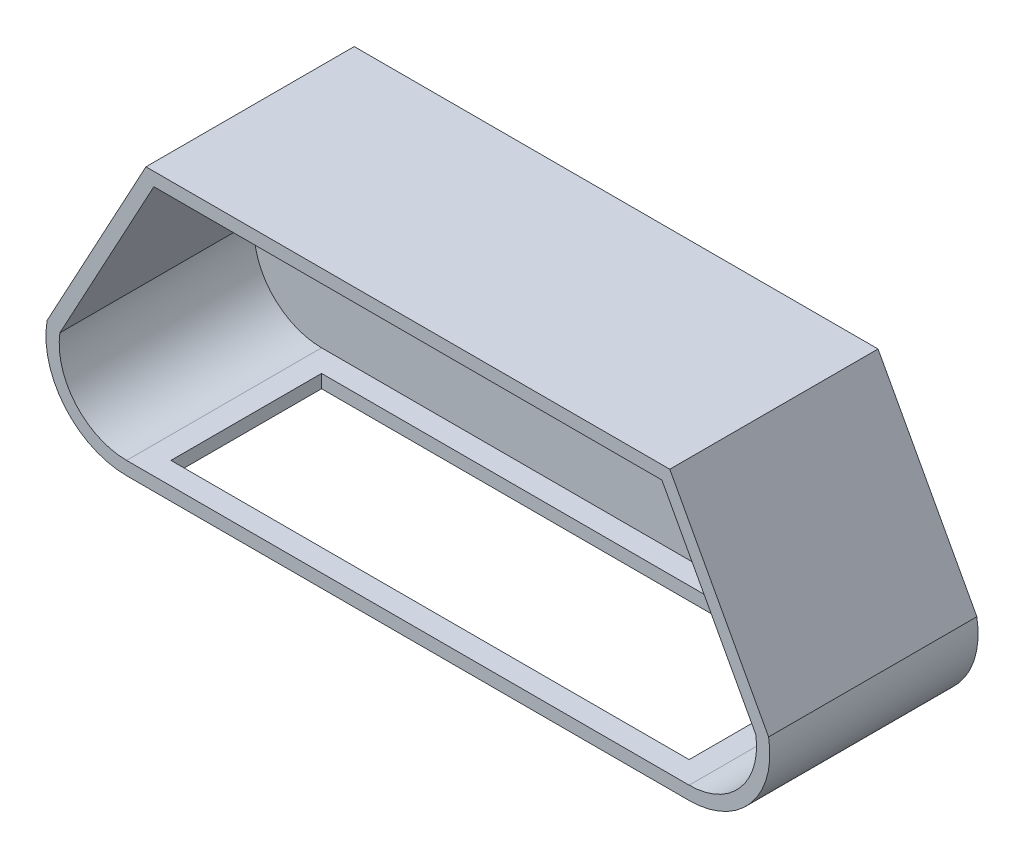
SolidWorks part; units mm, degrees
material "ABS"
ref_plane "Front Plane" through (0, 0, 0) normal (0, 0, 1) x (1, 0, 0)
ref_plane "Top Plane" through (0, 0, 0) normal (0, 1, 0) x (1, 0, 0)
ref_plane "Right Plane" through (0, 0, 0) normal (1, 0, 0) x (0, 0, -1)
sketch "Sketch1" plane through (0, 0, 0) normal (0, 0, 1) x (1, 0, 0)
  line L0 (101.3496, 25.9543) -> (-100.0805, 25.9543) construction
  line L1 (-100.0805, 25.9543) -> (-119.9586, -10.7438) construction
  line L2 (-119.9586, -10.7438) -> (121.2277, -10.7438) construction
  line L3 (121.2277, -10.7438) -> (101.3496, 25.9543) construction
  line L4 (98.8617, 30.5473) -> (-98.0902, 30.5473) construction
  line L5 (-98.0902, 30.5473) -> (-100.0805, 25.9543) construction
  line L6 (-100.0805, 25.9543) -> (101.3496, 25.9543) construction
  line L7 (101.3496, 25.9543) -> (98.8617, 30.5473) construction
  line L8 (121.2774, -10.8357) -> (-120.0083, -10.8357) construction
  line L9 (-120.0083, -10.8357) -> (-124.9592, -19.9757) construction
  line L10 (-124.9592, -19.9757) -> (126.2283, -19.9757) construction
  line L11 (126.2283, -19.9757) -> (121.2774, -10.8357) construction
  line L12 (126.2283, -19.9757) -> (-124.9592, -19.9757) construction
  line L13 (-124.9592, -19.9757) -> (-126.9495, -24.5687) construction
  line L14 (-126.9495, -24.5687) -> (128.7162, -24.5687) construction
  line L15 (128.7162, -24.5687) -> (126.2283, -19.9757) construction
  line L16 (-0.0149, 8.8786) -> (-0.0149, 16.2511) construction
  line L17 (-0.0149, 16.2511) -> (-21.6189, 32.8696) construction
  line L18 (-39.0554, 18.8331) -> (-15.5065, 0.7186) construction
  line L19 (-15.5065, 0.7186) -> (-8.5158, 0.7186) construction
  line L20 (-21.6189, 32.8696) -> (-0.0149, 16.2511) construction
  line L21 (-0.0149, 16.2511) -> (21.5891, 32.8696) construction
  line L22 (21.5891, 32.8696) -> (-21.6189, 32.8696) construction
  line L23 (-0.0149, 16.2511) -> (-0.0149, 8.8786) construction
  line L24 (8.4859, 0.7186) -> (15.4767, 0.7186) construction
  line L25 (15.4767, 0.7186) -> (39.0256, 18.8331) construction
  line L26 (21.5891, 32.8696) -> (-0.0149, 16.2511) construction
  line L27 (-0.0149, -7.4414) -> (-0.0149, -14.814) construction
  line L28 (-0.0149, -14.814) -> (21.5891, -31.4324) construction
  line L29 (39.0256, -17.396) -> (15.4767, 0.7186) construction
  line L30 (15.4767, 0.7186) -> (8.4859, 0.7186) construction
  line L31 (-0.0149, -14.814) -> (-0.0149, -7.4414) construction
  line L32 (-8.5158, 0.7186) -> (-15.5065, 0.7186) construction
  line L33 (-15.5065, 0.7186) -> (-39.0554, -17.396) construction
  line L34 (-21.6189, -31.4324) -> (-0.0149, -14.814) construction
  line L35 (21.5891, -31.4324) -> (-0.0149, -14.814) construction
  line L36 (-0.0149, -14.814) -> (-21.6189, -31.4324) construction
  line L37 (-21.6189, -31.4324) -> (21.5891, -31.4324) construction
  line L38 (0, 0) -> (0, -40) construction
  line L55 (118.2148, 64.1367) -> (-118.2148, 64.1367)
  line L56 (-162.8226, -18.2161) -> (-118.2148, 64.1367)
  line L57 (126.9495, -61) -> (-126.9495, -61)
  line L58 (162.8226, -18.2161) -> (118.2148, 64.1367)
  line L59 (114.6411, 58.1367) -> (-114.6411, 58.1367)
  line L60 (-157.0626, -20.1798) -> (-114.6411, 58.1367)
  line L61 (126.9495, -55) -> (-126.9495, -55)
  line L62 (157.0626, -20.1798) -> (114.6411, 58.1367)
  arc A7 (-126.9495, -61) -> (-162.8226, -18.2161) centre (-126.9495, -24.5687) cw
  arc A8 (126.9495, -61) -> (162.8226, -18.2161) centre (126.9495, -24.5687) ccw
  arc A9 (-126.9495, -55) -> (-157.0626, -20.1798) centre (-126.9495, -24.5687) cw
  arc A10 (126.9495, -55) -> (157.0626, -20.1798) centre (126.9495, -24.5687) ccw
  ellipse E0 centre (89.7353, -69.7395) end of major axis (186.1017, -143.8674) minor radius 36.744 (-8.4299, 0.9831) -> (-8.5158, 0.7186) ccw construction
  ellipse E1 centre (-34.244, 25.6292) end of major axis (23.2497, 27.2434) minor radius 7.0609 (-21.6189, 32.8696) -> (-29.9018, 32.7928) ccw construction
  ellipse E2 centre (-29.4366, 21.9312) end of major axis (-30.126, -23.328) minor radius 9.5952 (-38.9944, 23.9309) -> (-39.0554, 18.8331) ccw construction
  ellipse E3 centre (-89.7652, -69.7395) end of major axis (-186.1315, -143.8674) minor radius 36.744 (8.4859, 0.7186) -> (8.4, 0.9831) ccw construction
  ellipse E4 centre (29.4068, 21.9312) end of major axis (28.7173, 67.1904) minor radius 9.5952 (39.0256, 18.8331) -> (38.9645, 23.9309) ccw construction
  ellipse E5 centre (34.2141, 25.6292) end of major axis (91.7078, 24.015) minor radius 7.0609 (29.872, 32.7928) -> (21.5891, 32.8696) ccw construction
  ellipse E6 centre (-89.7652, 71.1766) end of major axis (-186.1315, 145.3046) minor radius 36.744 (8.4, 0.4541) -> (8.4859, 0.7186) ccw construction
  ellipse E7 centre (34.2141, -24.1921) end of major axis (91.7078, -22.5778) minor radius 7.0609 (21.5891, -31.4324) -> (29.872, -31.3556) ccw construction
  ellipse E8 centre (29.4068, -20.4941) end of major axis (28.7173, -65.7533) minor radius 9.5952 (38.9645, -22.4938) -> (39.0256, -17.396) ccw construction
  ellipse E9 centre (89.7353, 71.1766) end of major axis (186.1017, 145.3046) minor radius 36.744 (-8.5158, 0.7186) -> (-8.4299, 0.4541) ccw construction
  ellipse E10 centre (-29.4366, -20.4941) end of major axis (-30.126, 24.7651) minor radius 9.5952 (-39.0554, -17.396) -> (-38.9944, -22.4938) ccw construction
  ellipse E11 centre (-34.244, -24.1921) end of major axis (-91.7377, -22.5778) minor radius 7.0609 (-29.9018, -31.3556) -> (-21.6189, -31.4324) ccw construction
  spline S0 degree 3 poles (-8.4299, 0.9831) (-8.3473, 1.2284) (-8.2786, 1.4779) (-8.1305, 1.9735) (-8.0532, 2.2202) (-7.7992, 2.9534) (-7.601, 3.4303) (-7.1352, 4.3396) (-6.8677, 4.7742) (-6.2562, 5.5989) (-5.9092, 5.991) (-5.1648, 6.6958) (-4.7647, 7.013) (-3.91, 7.5786) (-3.451, 7.8283) (-2.509, 8.2452) (-2.0243, 8.4142) (-1.0325, 8.6872) (-0.5243, 8.7893) (-0.0149, 8.8786) knots 0 0 0 0 0.0625 0.0625 0.125 0.125 0.25 0.25 0.375 0.375 0.5 0.5 0.625 0.625 0.75 0.75 0.875 0.875 1 1 1 1 construction
  spline S1 degree 3 poles (-29.9018, 32.7928) (-30.49, 32.782) (-31.0692, 32.7181) (-31.9248, 32.5449) (-32.2077, 32.4742) (-32.769, 32.3061) (-33.0487, 32.208) (-33.8657, 31.8778) (-34.3832, 31.6099) (-35.1186, 31.1362) (-35.3569, 30.9662) (-35.8192, 30.6011) (-36.042, 30.4067) (-36.6741, 29.7983) (-37.0523, 29.3558) (-37.554, 28.6361) (-37.7109, 28.3855) (-37.998, 27.8717) (-38.1278, 27.6096) (-38.4772, 26.8083) (-38.6573, 26.2539) (-38.8469, 25.3922) (-38.8962, 25.1012) (-38.9663, 24.5182) (-38.9874, 24.2252) (-38.9944, 23.9309) knots 0 0 0 0 0.125 0.125 0.1875 0.1875 0.25 0.25 0.375 0.375 0.4375 0.4375 0.5 0.5 0.625 0.625 0.6875 0.6875 0.75 0.75 0.875 0.875 0.9375 0.9375 1 1 1 1 construction
  spline S2 degree 3 poles (-0.0149, 8.8786) (0.4936, 8.7894) (0.9992, 8.688) (1.9949, 8.4141) (2.4823, 8.2438) (3.416, 7.8307) (3.8648, 7.5877) (4.5082, 7.1636) (4.7189, 7.0113) (5.1236, 6.6907) (5.3175, 6.5226) (5.8747, 5.9957) (6.2134, 5.6143) (6.8262, 4.7918) (7.1004, 4.3485) (7.571, 3.4312) (7.7697, 2.9525) (8.0235, 2.2198) (8.1007, 1.9731) (8.2488, 1.4777) (8.3175, 1.2283) (8.4, 0.9831) knots 0 0 0 0 0.125 0.125 0.25 0.25 0.375 0.375 0.4375 0.4375 0.5 0.5 0.625 0.625 0.75 0.75 0.875 0.875 0.9375 0.9375 1 1 1 1 construction
  spline S3 degree 3 poles (38.9645, 23.9309) (38.9505, 24.5193) (38.8809, 25.0976) (38.6947, 25.9499) (38.619, 26.2314) (38.4391, 26.7893) (38.3345, 27.0665) (37.984, 27.8723) (37.7006, 28.3807) (37.0349, 29.34) (36.6487, 29.7934) (35.8081, 30.6037) (35.3512, 30.9659) (34.6108, 31.4447) (34.3545, 31.5934) (33.8344, 31.8633) (33.5692, 31.9853) (32.7589, 32.3137) (32.1969, 32.4832) (31.0426, 32.7181) (30.4599, 32.782) (29.872, 32.7928) knots 0 0 0 0 0.125 0.125 0.1875 0.1875 0.25 0.25 0.375 0.375 0.5 0.5 0.625 0.625 0.6875 0.6875 0.75 0.75 0.875 0.875 1 1 1 1 construction
  spline S4 degree 3 poles (8.4, 0.4541) (8.3174, 0.2088) (8.2488, -0.0408) (8.1006, -0.5364) (8.0233, -0.7831) (7.7694, -1.5162) (7.5712, -1.9931) (7.1053, -2.9025) (6.8378, -3.337) (6.2263, -4.1618) (5.8793, -4.5538) (5.1349, -5.2586) (4.7349, -5.5759) (3.8802, -6.1415) (3.4211, -6.3912) (2.4791, -6.8081) (1.9945, -6.977) (1.0027, -7.25) (0.4945, -7.3521) (-0.0149, -7.4414) knots 0 0 0 0 0.0625 0.0625 0.125 0.125 0.25 0.25 0.375 0.375 0.5 0.5 0.625 0.625 0.75 0.75 0.875 0.875 1 1 1 1 construction
  spline S5 degree 3 poles (29.872, -31.3556) (30.4601, -31.3448) (31.0394, -31.281) (31.8949, -31.1078) (32.1779, -31.0371) (32.7391, -30.869) (33.0188, -30.7709) (33.8358, -30.4407) (34.3533, -30.1728) (35.0888, -29.699) (35.3271, -29.529) (35.7893, -29.1639) (36.0121, -28.9695) (36.6443, -28.3612) (37.0224, -27.9187) (37.5241, -27.199) (37.6811, -26.9483) (37.9682, -26.4346) (38.098, -26.1725) (38.4474, -25.3711) (38.6274, -24.8168) (38.817, -23.955) (38.8663, -23.664) (38.9364, -23.081) (38.9575, -22.7881) (38.9645, -22.4938) knots 0 0 0 0 0.125 0.125 0.1875 0.1875 0.25 0.25 0.375 0.375 0.4375 0.4375 0.5 0.5 0.625 0.625 0.6875 0.6875 0.75 0.75 0.875 0.875 0.9375 0.9375 1 1 1 1 construction
  spline S6 degree 3 poles (-0.0149, -7.4414) (-0.5235, -7.3523) (-1.0291, -7.2509) (-2.0248, -6.977) (-2.5121, -6.8066) (-3.4458, -6.3935) (-3.8946, -6.1506) (-4.5381, -5.7264) (-4.7487, -5.5742) (-5.1535, -5.2536) (-5.3474, -5.0855) (-5.9046, -4.5586) (-6.2433, -4.1771) (-6.856, -3.3546) (-7.1303, -2.9113) (-7.6009, -1.9941) (-7.7996, -1.5153) (-8.0533, -0.7826) (-8.1306, -0.536) (-8.2787, -0.0406) (-8.3474, 0.2089) (-8.4299, 0.4541) knots 0 0 0 0 0.125 0.125 0.25 0.25 0.375 0.375 0.4375 0.4375 0.5 0.5 0.625 0.625 0.75 0.75 0.875 0.875 0.9375 0.9375 1 1 1 1 construction
  spline S7 degree 3 poles (-38.9944, -22.4938) (-38.9803, -23.0821) (-38.9107, -23.6604) (-38.7246, -24.5127) (-38.6488, -24.7943) (-38.469, -25.3522) (-38.3643, -25.6294) (-38.0139, -26.4352) (-37.7305, -26.9436) (-37.0648, -27.9029) (-36.6785, -28.3562) (-35.838, -29.1666) (-35.381, -29.5287) (-34.6407, -30.0075) (-34.3844, -30.1563) (-33.8642, -30.4261) (-33.5991, -30.5481) (-32.7888, -30.8765) (-32.2268, -31.046) (-31.0725, -31.2809) (-30.4898, -31.3448) (-29.9018, -31.3556) knots 0 0 0 0 0.125 0.125 0.1875 0.1875 0.25 0.25 0.375 0.375 0.5 0.5 0.625 0.625 0.6875 0.6875 0.75 0.75 0.875 0.875 1 1 1 1 construction
  point P124 (0, -50)
  dimension "D1" = 40
extrude "Boss-Extrude1" add sketch "Sketch1" along normal blind 88 contours L58 A7 A8 L56 L55 L57 A10 L61 A9 L60 L59 L62
sketch "Sketch3" plane through (0, -46, 0) normal (0, -1, 0) x (1, 0, 0)
  line L0 (-116.9495, 78) -> (116.9495, 78)
  line L1 (-126.9495, 88) -> (126.9495, 88)
  line L2 (-126.9495, 88) -> (-126.9495, 0)
  line L3 (-126.9495, 0) -> (126.9495, 0)
  line L4 (126.9495, 88) -> (126.9495, 0)
  line L5 (116.9495, 78) -> (116.9495, 10)
  line L6 (-116.9495, 10) -> (116.9495, 10)
  line L7 (-116.9495, 78) -> (-116.9495, 10)
  dimension "D1" = 10
extrude "Cut-Extrude1" cut sketch "Sketch3" along normal up to surface (15 mm away) contours L0 L7 L6 L5 region at (0, -46, 44) up to face at (0, -61, 44)
extrude "Boss-Extrude2" add sketch "Sketch1<12>" against normal blind 6 contours L61 A10 L62 L59 L60 A9 | L58 A7 A8 L56 L55 L57 A10 L61 A9 L60 L59 L62 region at (137.4421, 21.2938, 0) region at (0, -1.0155, 0)
sketch "Sketch1<12>" plane through (0, 0, 0) normal (0, 0, 1) x (1, 0, 0) same geometry as "Sketch1"
